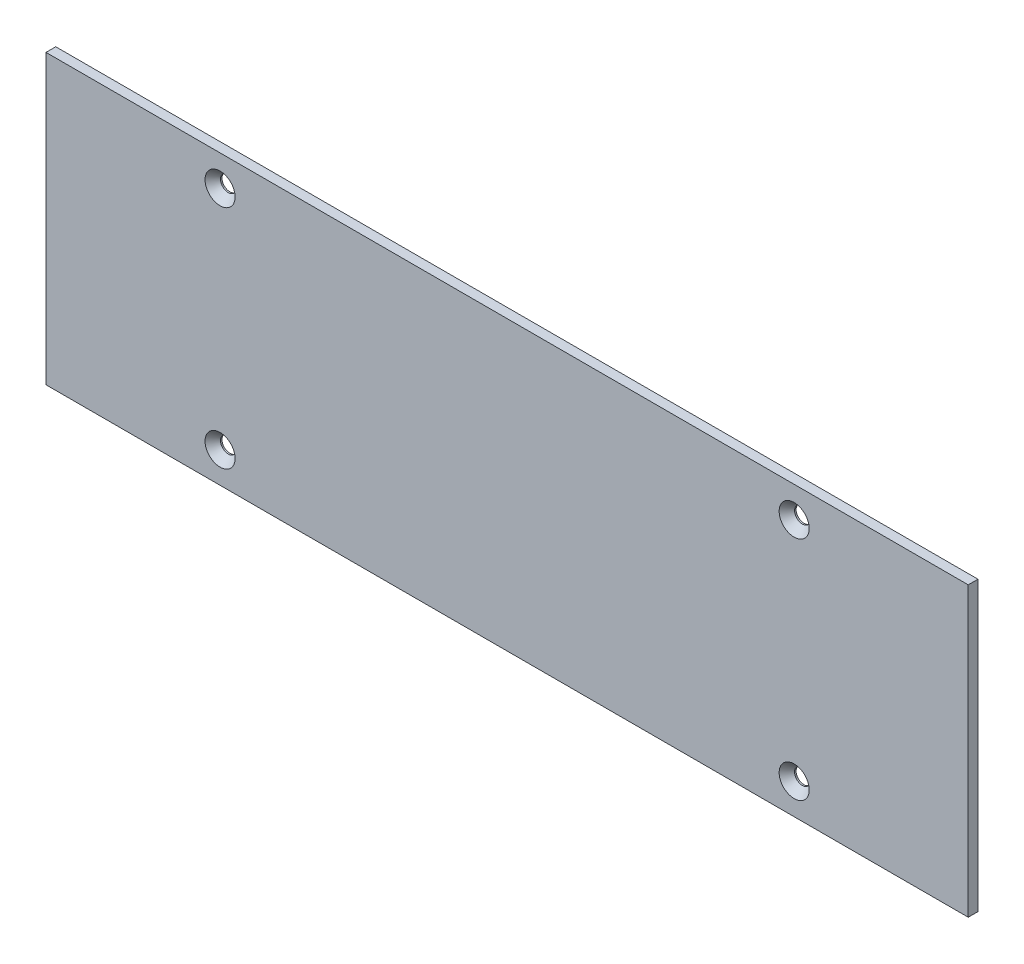
SolidWorks part; units mm, degrees
material "6061 Alloy"
ref_plane "Front Plane" through (0, 0, 0) normal (0, 0, 1) x (1, 0, 0)
ref_plane "Top Plane" through (0, 0, 0) normal (0, 1, 0) x (1, 0, 0)
ref_plane "Right Plane" through (0, 0, 0) normal (1, 0, 0) x (0, 0, -1)
sketch "Sketch1" plane through (0, 0, 0) normal (0, 0, 1) x (1, 0, 0)
  line L1 (-150, -46.825) -> (150, -46.825)
  line L2 (-150, -46.825) -> (-150, 46.825)
  line L3 (-150, 46.825) -> (150, 46.825)
  line L4 (150, -46.825) -> (150, 46.825)
  line L5 (-150, -46.825) -> (150, 46.825) construction
  line L6 (-150, 46.825) -> (150, -46.825) construction
  point P0 (0, 0)
  dimension "D1" = 300
  dimension "D2" = 93.65
extrude "Boss-Extrude1" add sketch "Sketch1" along normal blind 3.175
sketch "Sketch3" plane through (0, 0, 3.175) normal (0, 0, 1) x (1, 0, 0)
  point P0 (-93.375, 36.825)
  point P1 (93.375, 36.825)
  point P2 (93.375, -36.825)
  point P5 (-93.375, -36.825)
hole_wizard "CSK for #10 Flat Head Machine Screw1" positions "Sketch3" profile "Sketch4" countersink size "#10" standard "ANSI Inch"
sketch "Sketch4" plane through (-93.375, 36.825, 3.175) normal (1, 0, 0) x (0, -1, 0)
  line L0 (0, 0) -> (0, 6.3598)
  line L1 (0, 6.3598) -> (2.5527, 4.826)
  line L2 (2.5527, 4.826) -> (2.5527, 2.6882)
  line L3 (2.5527, 2.6882) -> (4.8895, 0)
  line L5 (4.8895, 0) -> (0, 0)
  line L6 (-2.5527, 2.6882) -> (-4.8895, 0) construction
  line L10 (0, 6.3598) -> (-2.5527, 4.826) construction
  line L11 (0, -6.35) -> (0, 107.95) construction
  dimension "Hole Dia." = 5.1054
  dimension "Hole Depth" = 4.826
  dimension "Near C'Sink Dia." = 9.779
  dimension "Near C'Sink Angle" = 82
  dimension "Drill Angle" = 118
equation "\"side\"= 100mm"
equation "\"thk\"= 1 / 8"
equation "\"D1@Sketch1\"=\"side\"*3"
equation "\"D2@Sketch1\"=\"side\"-(2*\"thk\")"
equation "\"D1@Boss-Extrude1\"=\"thk\""
